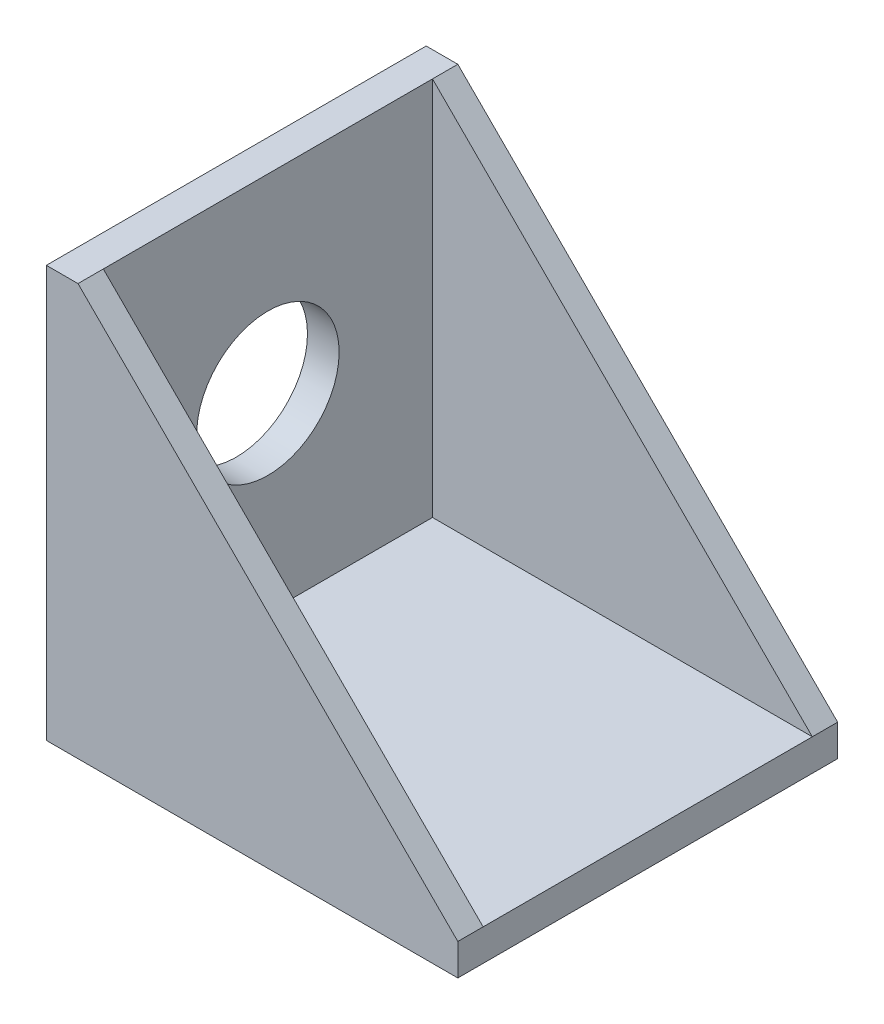
SolidWorks part; units mm, degrees
ref_plane "Front Plane" through (0, 0, 0) normal (0, 0, 1) x (1, 0, 0)
ref_plane "Top Plane" through (0, 0, 0) normal (0, 1, 0) x (1, 0, 0)
ref_plane "Right Plane" through (0, 0, 0) normal (1, 0, 0) x (0, 0, -1)
sketch "Sketch1" plane through (0, 0, 0) normal (1, 0, 0) x (0, 0, -1)
  line L5 (38.1, 38.1) -> (-38.1, 38.1)
  line L6 (38.1, 38.1) -> (38.1, -38.1)
  line L7 (38.1, -38.1) -> (-38.1, -38.1)
  line L8 (-38.1, 38.1) -> (-38.1, -38.1)
  line L9 (38.1, 38.1) -> (-38.1, -38.1) construction
  line L10 (38.1, -38.1) -> (-38.1, 38.1) construction
  line L11 (-38.1, -38.1) -> (38.1, -38.1)
  line L12 (-38.1, -38.1) -> (-38.1, -44.45)
  line L13 (-38.1, -44.45) -> (38.1, -44.45)
  line L14 (38.1, -38.1) -> (38.1, -44.45)
  circle A2 centre (0, 0) radius 14.2875
  dimension "D1" = 28.575
  dimension "D2" = 76.2
  dimension "D3" = 76.2
  dimension "D4" = 6.35
extrude "Boss-Extrude1" add sketch "Sketch1" along normal blind 76.2 contours L14 L7 L12 L13 region at (0, -41.275, 0)
extrude "Boss-Extrude2" add sketch "Sketch1<3>" against normal blind 6.35 separate body contours L5 L8 L7 L6 A2 region at (0, 0, -37.0224)
sketch "Sketch1<3>" plane through (0, 0, 0) normal (1, 0, 0) x (0, 0, -1) same geometry as "Sketch1"
sketch "Sketch3" plane through (0, -38.1, 0) normal (0, -1, 0) x (1, 0, 0)
  line L1 (-6.35, -38.1) -> (0, -38.1)
  line L2 (-6.35, -38.1) -> (-6.35, 38.1)
  line L3 (-6.35, 38.1) -> (0, 38.1)
  line L4 (0, -38.1) -> (0, 38.1)
extrude "Boss-Extrude3" add sketch "Sketch3" along normal blind 6.35 contours L2 L1 L4 L3
sketch "Sketch4" plane through (0, 0, 38.1) normal (0, 0, 1) x (1, 0, 0)
  line L0 (0, 38.1) -> (76.2, -38.1)
  line L1 (76.2, -38.1) -> (0, -38.1)
  line L2 (0, -38.1) -> (0, 38.1)
extrude "Boss-Extrude4" add sketch "Sketch4" against normal blind 5.08 contours L2 L0 L1
sketch "Sketch5" plane through (0, 0, -38.1) normal (0, 0, -1) x (-1, 0, 0)
  line L0 (0, 38.1) -> (-76.2, -38.1)
  line L1 (-76.2, -38.1) -> (0, -38.1)
  line L2 (0, -38.1) -> (0, 38.1)
extrude "Boss-Extrude5" add sketch "Sketch5" against normal blind 5.08
